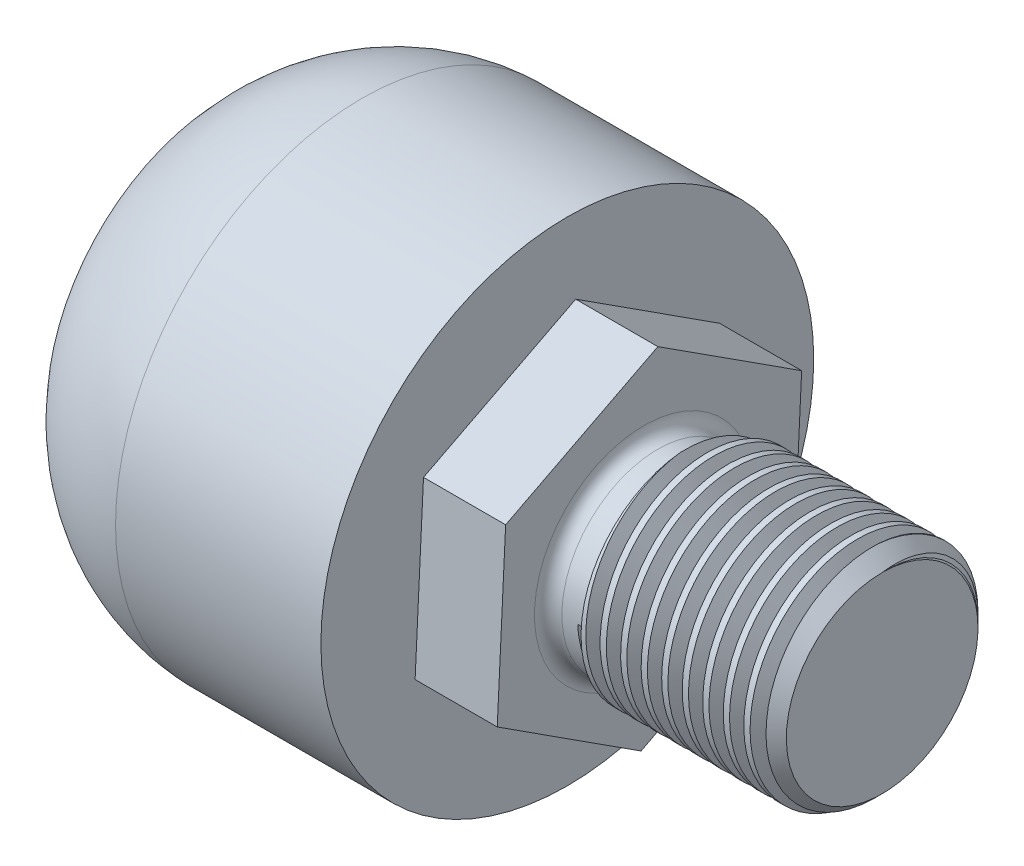
SolidWorks part; units mm, degrees
material "AISI 321 Annealed Stainless Steel (SS)"
ref_plane "Front Plane" through (0, 0, 0) normal (0, 0, 1) x (1, 0, 0)
ref_plane "Top Plane" through (0, 0, 0) normal (0, 1, 0) x (1, 0, 0)
ref_plane "Right Plane" through (0, 0, 0) normal (1, 0, 0) x (0, 0, -1)
sketch "Sketch1" plane through (0, 0, 0) normal (0, 0, 1) x (1, 0, 0)
  line L0 (-25, 13) -> (-23.9, 11.25)
  line L1 (-22.4, 10.75) -> (-23.9, 11.25)
  line L2 (-21.9133, 10.75) -> (-22.4, 10.75)
  line L3 (-14.5352, 13.65) -> (-15, 14)
  line L4 (-8.9, 13.75) -> (-14.5352, 13.65)
  line L5 (-8.9, 13.75) -> (-8.0352, 12)
  line L6 (-0.1535, 1.75) -> (-0.1535, 0)
  line L7 (0, 18) -> (0, 0)
  line L8 (0, 18) -> (-15, 18)
  line L9 (-0.1535, 0) -> (0, 0)
  arc A0 (-15, 18) -> (-25, 13) centre (-14.3013, 4.1026) ccw
  arc A1 (-15, 14) -> (-21.9133, 10.75) centre (-13.414, 1.6483) ccw
  arc A2 (-0.1535, 1.75) -> (-8.0352, 12) centre (-13.2264, -0.147) ccw
revolve "Revolve1" add sketch "Sketch1" angle 360 about L9
sketch "Sketch2" plane through (0, 0, 0) normal (1, 0, 0) x (0, 0, -1)
  line L1 (-0.6134, -12.4846) -> (10.5053, -6.7735)
  line L2 (10.5053, -6.7735) -> (11.1186, 5.7111)
  line L3 (11.1186, 5.7111) -> (0.6134, 12.4846)
  line L4 (0.6134, 12.4846) -> (-10.5053, 6.7735)
  line L5 (-10.5053, 6.7735) -> (-11.1186, -5.7111)
  line L6 (-11.1186, -5.7111) -> (-0.6134, -12.4846)
  circle A0 centre (0, 0) radius 10.825 construction
extrude "Boss-Extrude1" add sketch "Sketch2" along normal blind 6
sketch "Sketch3" plane through (6, 0, 0) normal (1, 0, 0) x (0, 0, -1)
  circle A0 centre (0, 0) radius 8
extrude "Boss-Extrude2" add sketch "Sketch3" along normal blind 17
chamfer "Pah1" distance 1 angle 45 1 edges at (23, 0, -8)
sketch "Sketch4" plane through (23, 0, 0) normal (1, 0, 0) x (0, 0, -1)
  circle A0 centre (0, 0) radius 8 construction
  circle A1 centre (0, 0) radius 8
curve "Helis/Spiral1" pitch 1.5 height 14.625 radius 8 centre (23, 0, 0) axis (-1, 0, 0) start towards (0, 1, 0)
sketch "Sketch5" plane through (0, 0, 0) normal (0, 0, 1) x (1, 0, 0)
  line L0 (23, 7) -> (22.09, 8.7481)
  line L1 (22.09, 8.7481) -> (23.91, 8.7481)
  line L2 (23.91, 8.7481) -> (23, 7)
  line L4 (23, -7) -> (23, 7) construction
  dimension "D1" = 55
  dimension "D2" = 27.5
  dimension "D3" = 1
sweep "Swept Cut2" cut profiles "Sketch5" path "Helis/Spiral1" align with end faces yes
sketch "Sketch6" plane through (6, 0, 0) normal (1, 0, 0) x (0, 0, -1)
  circle A0 centre (-0.3975, 0) radius 7
  circle A1 centre (-0.3975, 0) radius 14.6273
extrude "Kes-Ekstrüzyon1" cut sketch "Sketch6" along normal blind 3
fillet "Radyus1" radius 1 1 edges at (6, 0, -6.6025)
